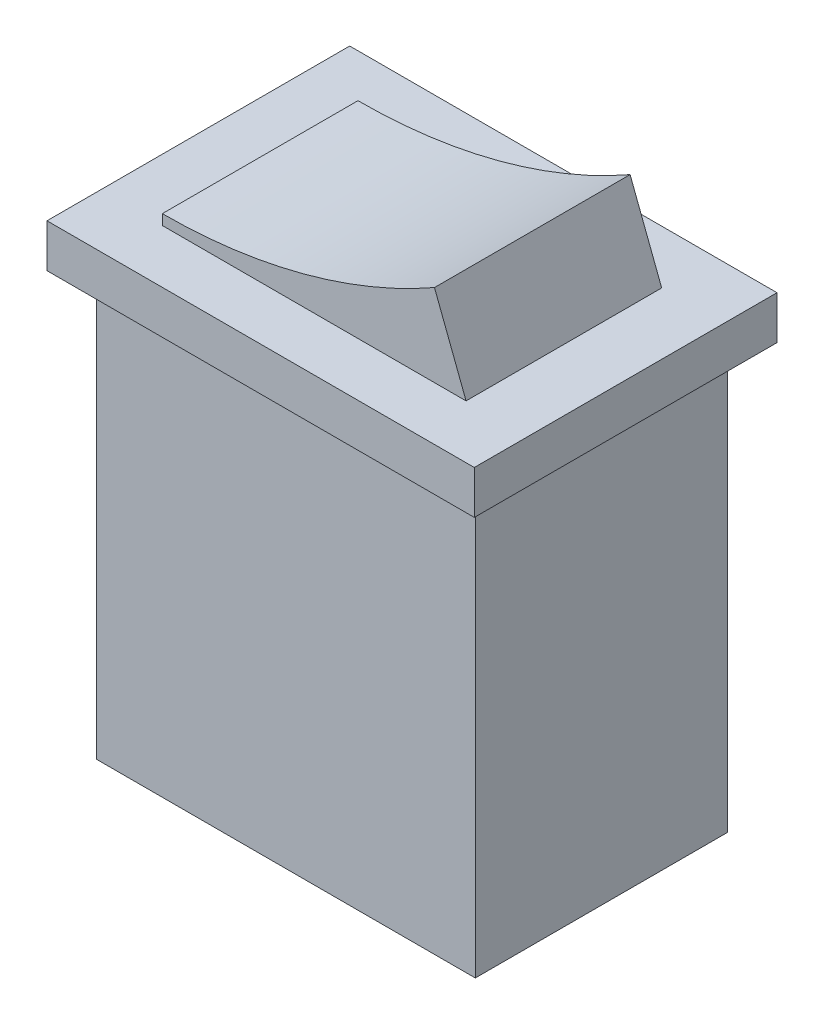
SolidWorks part; units mm, degrees
ref_plane "Front Plane" through (0, 0, 0) normal (0, 0, 1) x (1, 0, 0)
ref_plane "Top Plane" through (0, 0, 0) normal (0, 1, 0) x (1, 0, 0)
ref_plane "Right Plane" through (0, 0, 0) normal (1, 0, 0) x (0, 0, -1)
sketch "Sketch1" plane through (0, 0, 0) normal (0, 0, 1) x (1, 0, 0)
  line L0 (-7.375, 12.385) -> (-7.375, 12.885)
  line L1 (10.375, 12.385) -> (-10.375, 12.385)
  line L2 (10.375, 12.385) -> (10.375, 10.285)
  line L3 (10.375, 10.285) -> (-10.375, 10.285)
  line L4 (-10.375, 12.385) -> (-10.375, 10.285)
  line L5 (10.375, 12.385) -> (-10.375, 10.285) construction
  line L6 (10.375, 10.285) -> (-10.375, 12.385) construction
  line L7 (-9.2, -10.285) -> (9.2, -10.285)
  line L8 (-9.2, -10.285) -> (-9.2, 10.285)
  line L9 (-9.2, 10.285) -> (9.2, 10.285)
  line L10 (9.2, -10.285) -> (9.2, 10.285)
  line L11 (-9.2, -10.285) -> (9.2, 10.285) construction
  line L12 (-9.2, 10.285) -> (9.2, -10.285) construction
  line L13 (5.841, 16.385) -> (7.375, 12.385)
  arc A0 (-7.375, 12.885) -> (5.841, 16.385) centre (-7.375, 39.5866) ccw
  point P0 (0, 11.335)
  point P5 (0, 0)
  dimension "D9" = 26.7016
  dimension "D1" = 2.1
  dimension "D2" = 20.57
  dimension "D3" = 18.4
  dimension "D4" = 20.75
  dimension "D5" = 3
  dimension "D6" = 3
  dimension "D7" = 4
  dimension "D8" = 0.5
extrude "Boss-Extrude1" add sketch "Sketch1" along normal blind 6.125 and the other way blind 6.125 contours L7 L10 L9 L8
extrude "Boss-Extrude2" add sketch "Sketch1<3>" along normal blind 7.35 and the other way blind 7.35 contours L1 L4 L3 L2 region at (0, 11.335, 0)
sketch "Sketch1<3>" plane through (0, 0, 0) normal (0, 0, 1) x (1, 0, 0) same geometry as "Sketch1"
extrude "Boss-Extrude3" add sketch "Sketch1<4>" along normal blind 4.75 and the other way blind 4.75 contours A0 L0 L1 L13 region at (2.1537, 13.5519, 0)
sketch "Sketch1<4>" plane through (0, 0, 0) normal (0, 0, 1) x (1, 0, 0) same geometry as "Sketch1"
